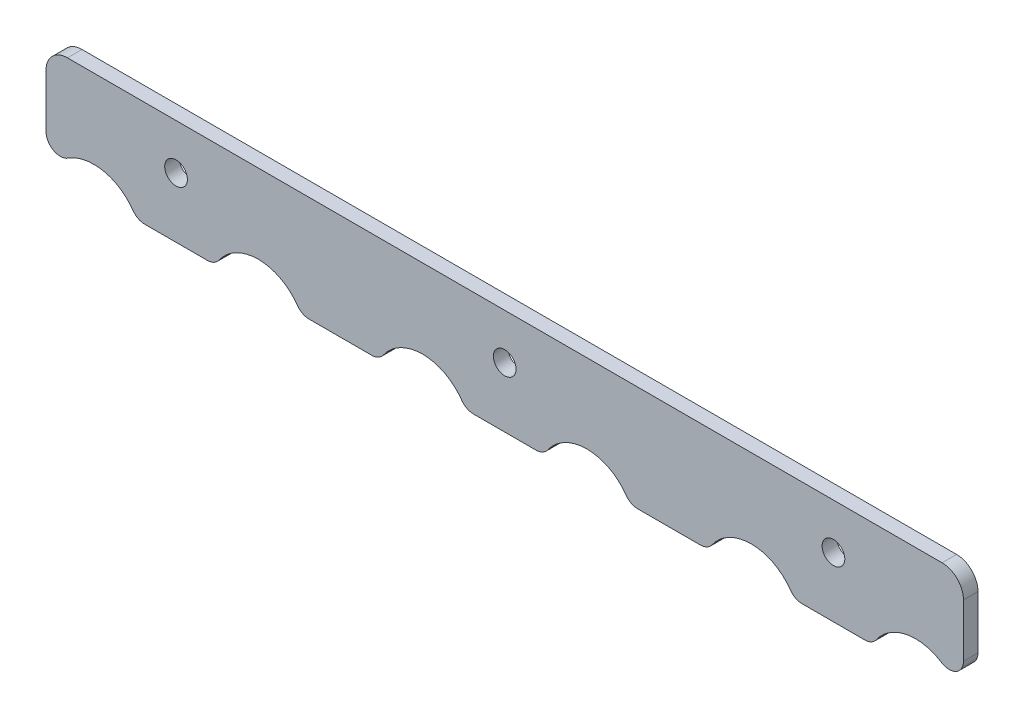
SolidWorks part; units mm, degrees
material "3003-H14"
ref_plane "X-Y Datum" through (0, 0, 0) normal (0, 0, 1) x (1, 0, 0)
ref_plane "X-Z Datum" through (0, 0, 0) normal (0, 1, 0) x (1, 0, 0)
ref_plane "Y-Z Datum" through (0, 0, 0) normal (1, 0, 0) x (0, 0, -1)
sketch "Sketch3" plane through (0, 0, 0) normal (0, 0, 1) x (1, 0, 0)
  line L1 (0, 0) -> (156.4633, 0) construction
  line L2 (0, 0) -> (0, 56.3098) construction
  line L3 (0, 56.3098) -> (156.4633, 56.3098) construction
  line L4 (156.4633, 0) -> (156.4633, 56.3098) construction
  line L5 (4.075, 10.775) -> (4.075, 28.535)
  line L6 (4.075, 28.535) -> (132.475, 28.535)
  line L7 (132.475, 28.535) -> (132.475, 10.775)
  line L9 (4.075, 13.775) -> (132.475, 13.775)
  line L10 (10.775, 10.775) -> (33.775, 10.775) construction
  line L11 (56.775, 10.775) -> (33.775, 10.775) construction
  line L48 (56.775, 10.775) -> (125.775, 10.775) construction
  circle A0 centre (10.775, 10.775) radius 10.775 construction
  circle A1 centre (33.775, 10.775) radius 10.775 construction
  circle A5 centre (56.775, 10.775) radius 10.775 construction
  circle A6 centre (10.775, 10.775) radius 4.7 construction
  circle A7 centre (33.775, 10.775) radius 4.7 construction
  circle A8 centre (56.775, 10.775) radius 4.7 construction
  circle A12 centre (79.775, 10.775) radius 10.775 construction
  circle A13 centre (79.775, 10.775) radius 4.7 construction
  circle A14 centre (102.775, 10.775) radius 10.775 construction
  circle A15 centre (102.775, 10.775) radius 4.7 construction
  circle A16 centre (125.775, 10.775) radius 10.775 construction
  circle A17 centre (125.775, 10.775) radius 4.7 construction
  circle A18 centre (125.775, 10.775) radius 10.775 construction
  circle A19 centre (102.775, 10.775) radius 10.775 construction
  circle A20 centre (79.775, 10.775) radius 10.775 construction
  circle A25 centre (10.775, 10.775) radius 6.7
  circle A26 centre (33.775, 10.775) radius 6.7
  circle A27 centre (56.775, 10.775) radius 6.7
  circle A28 centre (79.775, 10.775) radius 6.7
  circle A29 centre (102.775, 10.775) radius 6.7
  circle A30 centre (125.775, 10.775) radius 6.7
  dimension "D1" = 21.55
  dimension "D9" = 9.4
  dimension "D2" = 23
  dimension "D3" = 2
  dimension "D4" = 14.76
  dimension "D8" = 23
  dimension "D11" = 23
  dimension "D5" = 3
  dimension "D10" = 4
  dimension "D7" = 5
extrude "Boss-Extrude1" add sketch "Sketch3" along normal blind 2.032 contours A30 L9 L7 L6 L5 A25 A26 A27 A28 A29 | A25 L9 L5 | A30 L7 L9 region at (4.2857, 13.0332, 0) region at (68.275, 21.8085, 0) region at (132.2643, 13.0332, 0)
fillet "Fillet1" radius 3 2 edges at (4.075, 28.535, 1.016) (132.475, 28.535, 1.016)
fillet "Fillet2" radius 2 12 edges at (132.475, 10.775, 1.016) (119.7842, 13.775, 1.016) (108.7658, 13.775, 1.016) (96.7842, 13.775, 1.016) (85.7658, 13.775, 1.016) (73.7842, 13.775, 1.016) (62.7658, 13.775, 1.016) (50.7842, 13.775, 1.016) (39.7658, 13.775, 1.016) (27.7842, 13.775, 1.016) (16.7658, 13.775, 1.016) (4.075, 10.775, 1.016)
sketch "Sketch4" plane through (0, 0, 0) normal (0, 0, -1) x (-1, 0, 0)
  line L0 (-132.475, 22.185) -> (-4.075, 22.185) construction
  line L1 (-132.475, 25.535) -> (-132.475, 18.0962) construction
  line L2 (-4.075, 18.0962) -> (-4.075, 25.535) construction
  line L3 (-7.075, 28.535) -> (-129.475, 28.535) construction
  line L4 (-68.275, 28.535) -> (-68.275, 13.775) construction
  line L5 (-63.8947, 13.775) -> (-72.6553, 13.775) construction
  line L6 (-68.275, 22.185) -> (-4.075, 22.185) construction
  line L7 (-22.275, 13.775) -> (-22.275, 28.535) construction
  line L8 (-17.8947, 13.775) -> (-26.6553, 13.775) construction
  line L9 (-114.275, 13.775) -> (-114.275, 28.535) construction
  line L10 (-109.8947, 13.775) -> (-118.6553, 13.775) construction
  circle A0 centre (-22.275, 22.185) radius 1.5875
  circle A1 centre (-68.275, 22.185) radius 1.5875
  circle A3 centre (-114.275, 22.185) radius 1.5875
  point P30 (-68.275, 22.185)
  dimension "D1" = 3.175
  dimension "D2" = 6.35
extrude "Cut-Extrude1" cut sketch "Sketch4" against normal through all
